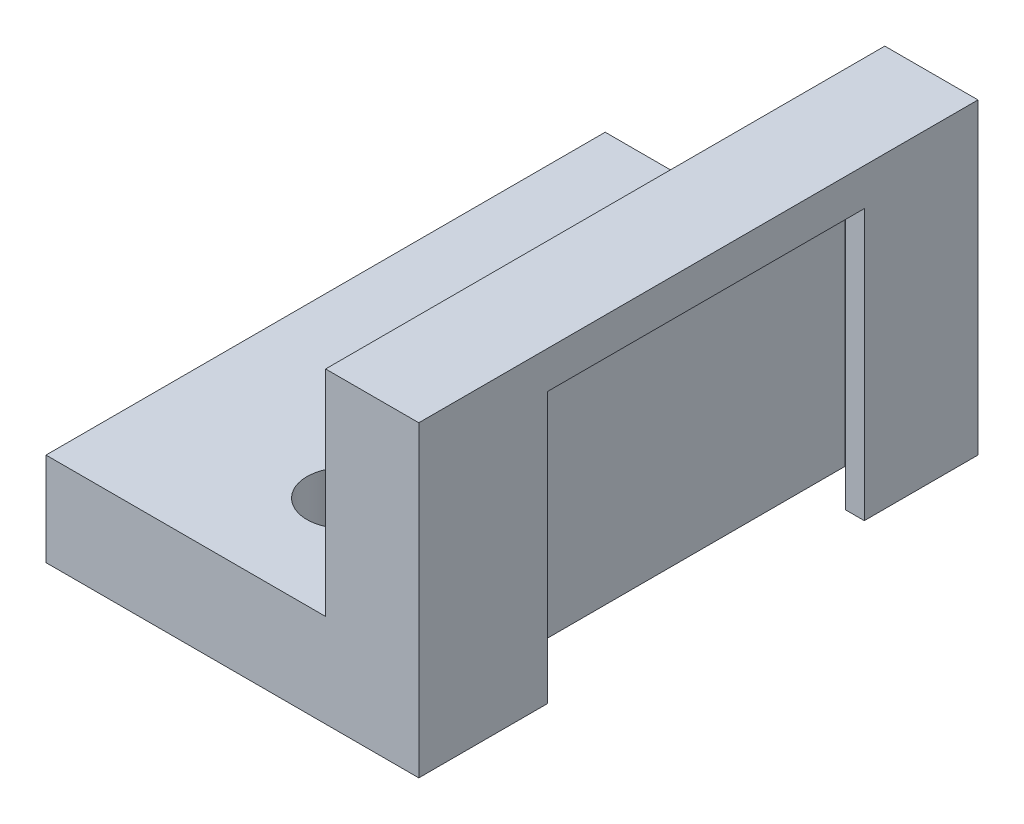
SolidWorks part; units mm, degrees
ref_plane "Alzado" through (0, 0, 0) normal (0, 0, 1) x (1, 0, 0)
ref_plane "Planta" through (0, 0, 0) normal (0, 1, 0) x (1, 0, 0)
ref_plane "Vista lateral" through (0, 0, 0) normal (1, 0, 0) x (0, 0, -1)
sketch "Croquis1" plane through (0, 0, 0) normal (0, 0, 1) x (1, 0, 0)
  line L3 (20, 0) -> (20, 14.5)
  line L4 (20, 14.5) -> (15, 14.5)
  line L5 (15, 14.5) -> (15, 5)
  line L6 (15, 5) -> (0, 5)
  line L7 (0, 5) -> (0, 0)
  line L8 (0, 0) -> (20, 0)
  dimension "D1" = 5
  dimension "D2" = 15
  dimension "D3" = 9.5
  dimension "D5" = 5
extrude "Saliente-Extruir1" add sketch "Croquis1" along normal blind 30
sketch "Croquis2" plane through (0, 14.5, 0) normal (0, 1, 0) x (1, 0, 0)
  line L0 (20, -15) -> (20, -23.1)
  line L1 (20, -30) -> (20, 0) construction
  line L2 (20, -6.1) -> (19, -6.1)
  line L3 (20, -23.1) -> (19, -23.1)
  line L4 (19, -23.1) -> (19, -25.1)
  line L5 (19, -25.1) -> (16.96, -25.1)
  line L6 (16.96, -25.1) -> (16.96, -4.1)
  line L8 (20, -30) -> (15, -30) construction
  line L9 (6.96, -15.4) -> (7.948, -15.4) construction
  line L10 (19, -4.1) -> (16.96, -4.1)
  line L11 (19, -6.1) -> (19, -4.1)
  line L12 (20, -23.1) -> (20, -6.1)
  line L13 (20, -6.1) -> (20, -15)
  line L15 (16.96, -4.1) -> (16.96, 0) construction
  line L16 (20, 0) -> (15, 0) construction
  point P6 (19, -4.1)
  line M11 (20, -30) -> (20, 0)
  dimension "D1" = 2.04
  dimension "D2" = 1
  dimension "D3" = 2
  dimension "D4" = 4.9
  dimension "D5" = 21
  dimension "D6" = 1
  dimension "D7" = 2
extrude "Cortar-Extruir1" cut sketch "Croquis2" against normal up to next contours L2 L11 L10 L6 L5 L4 L3 M11 region at (18.4118, 14.5, 14.6)
sketch "Croquis3" plane through (0, 5, 0) normal (0, 1, 0) x (1, 0, 0)
  line L0 (10, 0) -> (10, -6) construction
  line L1 (10, -6) -> (15, -6) construction
  line L2 (15, -30) -> (15, 0) construction
  line L5 (0, -30) -> (0, 0) construction
  line L6 (0, -15) -> (2.5, -15) construction
  circle A0 centre (10, -6) radius 2
  circle A1 centre (10, -24) radius 2
  dimension "D1" = 4
  dimension "D2" = 6
  dimension "D3" = 5
extrude "Cortar-Extruir2" cut sketch "Croquis3" against normal up to next
sketch "Croquis4" plane through (0, 0, 0) normal (0, -1, 0) x (1, 0, 0)
  line L0 (0, 15) -> (2.5455, 15) construction
  line L1 (0, 30) -> (0, 0) construction
  circle A2 centre (10, 24) radius 3.25
  circle A3 centre (10, 6) radius 3.25
  dimension "D1" = 6.5
extrude "Cortar-Extruir3" cut sketch "Croquis4" against normal blind 2
sketch "Croquis5" plane through (0, 14.5, 0) normal (0, 1, 0) x (1, 0, 0)
  line L1 (15, 0) -> (20, 0)
  line L2 (15, 0) -> (15, -30)
  line L3 (15, -30) -> (20, -30)
  line L4 (20, 0) -> (20, -30)
extrude "Saliente-Extruir2" add sketch "Croquis5" along normal blind 2
